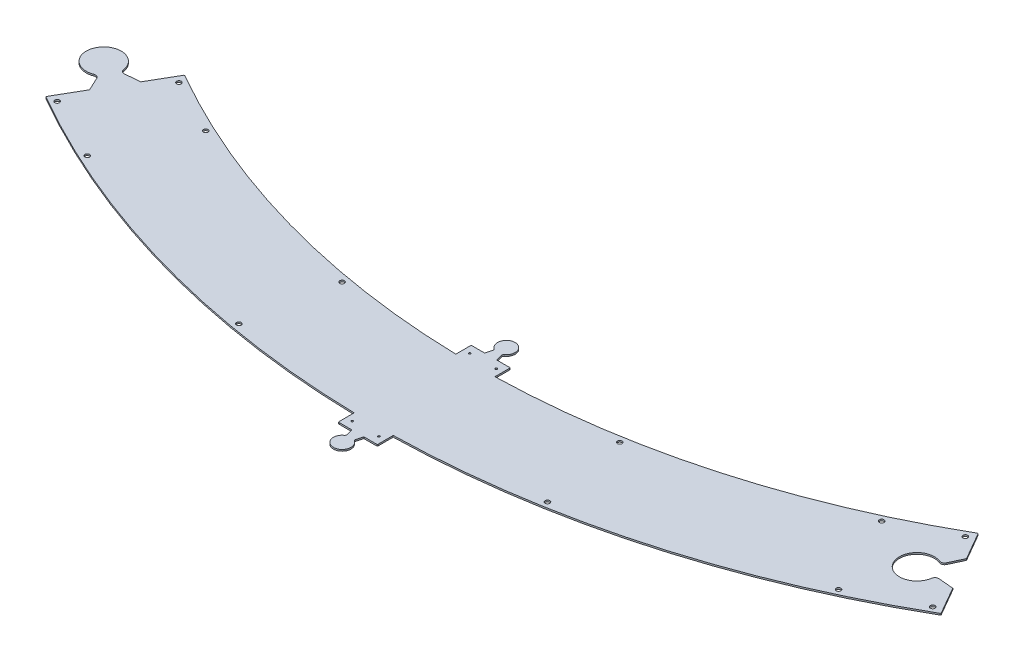
SolidWorks part; units mm, degrees
ref_plane "Front Plane" through (0, 0, 0) normal (0, 0, 1) x (1, 0, 0)
ref_plane "Top Plane" through (0, 0, 0) normal (0, 1, 0) x (1, 0, 0)
ref_plane "Right Plane" through (0, 0, 0) normal (1, 0, 0) x (0, 0, -1)
sketch "Sketch1" plane through (0, 0, 0) normal (0, 1, 0) x (1, 0, 0)
  line L0 (0, 0) -> (0, -1145) construction
  line L1 (0, 0) -> (-572.5, -991.5991) construction
  line L2 (0, 0) -> (572.5, -991.5991) construction
  line L3 (507.5, -879.0158) -> (572.5, -991.5991)
  line L5 (-25, -1014.6921) -> (-25, -995)
  line L6 (-25, -995) -> (25, -995)
  line L7 (25, -1014.6921) -> (25, -995)
  line L8 (-507.5, -879.0158) -> (-572.5, -991.5991)
  line L9 (0, 0) -> (480.4042, -1030.5245) construction
  line L10 (507.5, -879.0158) -> (511.7433, -876.5659) construction
  line L11 (572.5, -991.5991) -> (576.3111, -989.3987) construction
  line L12 (-25, -1165) -> (25, -1165)
  line L13 (-25, -1165) -> (-25, -1144.727)
  line L14 (25, -1165) -> (25, -1144.727)
  arc A0 (-572.5, -991.5991) -> (-25, -1144.727) centre (0, 0) ccw
  arc A1 (-507.5, -879.0158) -> (-25, -1014.6921) centre (0, 0) ccw
  arc A2 (25, -1014.6921) -> (507.5, -879.0158) centre (0, 0) ccw
  arc A3 (-507.5, -879.0158) -> (507.5, -879.0158) centre (0, 0) ccw construction
  circle A4 centre (-17, -1005) radius 1.25
  circle A5 centre (17, -1005) radius 1.25
  arc A7 (25.197, -1022.6896) -> (511.5, -885.944) centre (0, 0) ccw construction
  circle A8 centre (502.8397, -890.944) radius 3
  arc A9 (-568.5, -984.6709) -> (568.5, -984.6709) centre (0, 0) ccw construction
  circle A10 centre (559.8397, -989.6709) radius 3
  circle A22 centre (480.4042, -1030.5245) radius 3
  arc A37 (25, -1144.727) -> (572.5, -991.5991) centre (0, 0) ccw
  circle A38 centre (432.237, -927.2002) radius 3
  arc A39 (-572.5, -991.5991) -> (572.5, -991.5991) centre (0, 0) ccw construction
  circle A40 centre (-17, -1155) radius 1.25
  circle A42 centre (17, -1155) radius 1.25
  circle A43 centre (177.5319, -1007.4778) radius 3
  circle A44 centre (197.3155, -1119.748) radius 3
  circle A47 centre (-89.2718, -1019.0974) radius 3 [skipped]
  circle A48 centre (-99.22, -1132.6625) radius 3 [skipped]
  circle A49 centre (-559.8397, -989.6709) radius 3
  circle A50 centre (-502.8397, -890.944) radius 3
  circle A51 centre (-480.4042, -1030.5245) radius 3
  circle A52 centre (-432.237, -927.2002) radius 3
  circle A53 centre (-197.3155, -1119.748) radius 3
  circle A54 centre (-177.5319, -1007.4778) radius 3
  point P5 (0, -995)
  point P34 (0, -1165)
  point P50 (0, 0)
  point P52 (0, 0)
  point P71 (0, 0)
  dimension "D2" = 1145
  dimension "D4" = 2.5
  dimension "D9" = 8
  dimension "D10" = 6
  dimension "D12" = 8
  dimension "D13" = 10
  dimension "D14" = 50
  dimension "D15" = 20
  dimension "D16" = 99.22
  dimension "D19" = 8
  dimension "D21" = 3
  dimension "D1" = 30
  dimension "D3" = 50
  dimension "D5" = 150
  dimension "D7" = 10
  dimension "D8" = 8
  dimension "D11" = 10
  dimension "D17" = 8
  dimension "D18" = 8
  dimension "D20" = 10
  dimension "D6" = 130
extrude "Boss-Extrude2" add sketch "Sketch1" along normal blind 2
ref_axis "Axis1" through (0, 2.1, 0) along (0, -1, 0)
fillet "Fillet1" radius 1 8 edges at (-507.5, 1, 879.0158) (-572.5, 1, 991.5991) (-25, 1, 1165) (25, 1, 1165) (-25, 1, 995) (25, 1, 995) (507.5, 1, 879.0158) (572.5, 1, 991.5991)
sketch "Sketch3" plane through (0, 2, 0) normal (0, 1, 0) x (1, 0, 0)
  line L0 (539.9998, -935.307) -> (505.3588, -955.307) construction
  line L2 (571.9998, -990.7327) -> (507.9998, -879.8814) construction
  line L3 (522.6793, -945.307) -> (517.6793, -936.6468) construction
  line L4 (519.8717, -931.9451) -> (527.9977, -914.5188)
  line L5 (532.8473, -954.4194) -> (552.0018, -956.0952)
  line L6 (527.9977, -914.5188) -> (552.0018, -956.0952)
  arc A0 (513.5161, -934.4874) -> (527.4678, -958.6524) centre (505.3588, -955.307) ccw
  arc A1 (513.5161, -934.4874) -> (519.8717, -931.9451) centre (515.3402, -929.832) ccw
  arc A2 (532.8473, -954.4194) -> (527.4678, -958.6524) centre (532.4115, -959.4004) ccw
  point P14 (527.6793, -953.9673)
  dimension "D5" = 5
  dimension "D1" = 40
  dimension "D2" = 10
  dimension "D3" = 20
  dimension "D4" = 35
extrude "Cut-Extrude1" cut sketch "Sketch3" against normal up to surface (2 mm away) up to face at (0, 0, 1028.5982)
sketch "Sketch4" plane through (0, 2, 0) normal (0, 1, 0) x (1, 0, 0)
  line L0 (-539.9998, -935.307) -> (-574.6408, -915.307) construction
  line L1 (-507.9998, -879.8814) -> (-571.9998, -990.7327) construction
  line L2 (-557.3203, -925.307) -> (-552.3203, -916.6468) construction
  line L3 (-547.1523, -916.1946) -> (-527.9977, -914.5188)
  line L4 (-560.1278, -938.669) -> (-552.0018, -956.0952)
  line L5 (-527.9977, -914.5188) -> (-552.0018, -956.0952)
  line L6 (0, -995) -> (0, -975) construction
  line L7 (24, -995) -> (-24, -995) construction
  line L8 (0, -985) -> (5, -985) construction
  line L9 (5.4863, -986.815) -> (7.6795, -995)
  line L10 (-5.4863, -986.815) -> (-7.6795, -995)
  line L11 (-7.6795, -995) -> (7.6795, -995)
  line L12 (0, -995) -> (0, -1165) construction
  line L13 (-24, -1165) -> (24, -1165) construction
  line L14 (0, -1080) -> (33.8394, -1080) construction
  line L15 (0, -1175) -> (5, -1175) construction
  line L16 (0, -1165) -> (0, -1185) construction
  line L17 (-7.6795, -1165) -> (7.6795, -1165)
  line L18 (-5.4863, -1173.185) -> (-7.6795, -1165)
  line L19 (5.4863, -1173.185) -> (7.6795, -1165)
  arc A0 (-552.5318, -911.9617) -> (-566.4834, -936.1267) centre (-574.6408, -915.307) ccw
  arc A1 (-560.1278, -938.669) -> (-566.4834, -936.1267) centre (-564.6594, -940.7821) ccw
  arc A2 (-552.5318, -911.9617) -> (-547.1523, -916.1946) centre (-547.588, -911.2137) ccw
  arc A3 (6.4573, -984.1271) -> (-6.4573, -984.1271) centre (0, -975) ccw
  arc A4 (6.4573, -984.1271) -> (5.4863, -986.815) centre (7.9011, -986.168) ccw
  arc A5 (-5.4863, -986.815) -> (-6.4573, -984.1271) centre (-7.9011, -986.168) ccw
  arc A6 (-5.4863, -1173.185) -> (-6.4573, -1175.8729) centre (-7.9011, -1173.832) cw
  arc A7 (6.4573, -1175.8729) -> (5.4863, -1173.185) centre (7.9011, -1173.832) cw
  arc A8 (6.4573, -1175.8729) -> (-6.4573, -1175.8729) centre (0, -1185) cw
  point P11 (-562.3203, -933.9673)
  point P30 (-5, -985)
  point P47 (-5, -1175)
  dimension "D5" = 5
  dimension "D9" = 2.5
  dimension "D1" = 40
  dimension "D2" = 10
  dimension "D3" = 20
  dimension "D4" = 35
  dimension "D6" = 20
  dimension "D7" = 5
  dimension "D8" = 15
extrude "Boss-Extrude3" add sketch "Sketch4" against normal up to surface (2 mm away) up to face at (120.7258, 0, 1009.3152)
